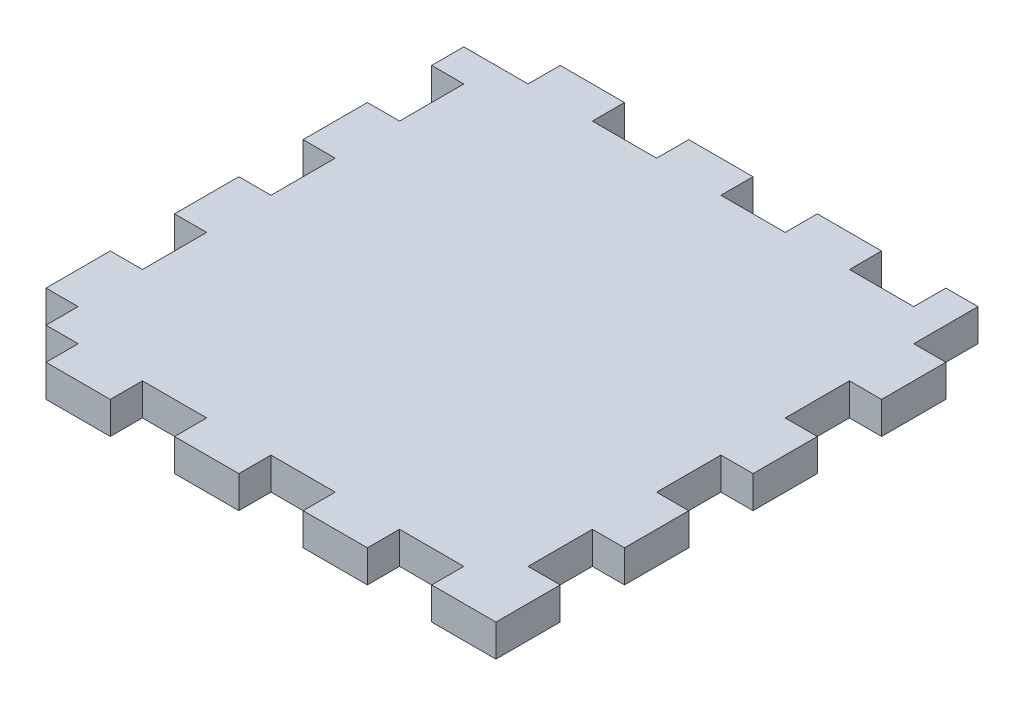
SolidWorks part; units mm, degrees
ref_plane "Front Plane" through (0, 0, 0) normal (0, 0, 1) x (1, 0, 0)
ref_plane "Top Plane" through (0, 0, 0) normal (0, 1, 0) x (1, 0, 0)
ref_plane "Right Plane" through (0, 0, 0) normal (1, 0, 0) x (0, 0, -1)
sketch "Sketch1" plane through (0, 0, 0) normal (0, 1, 0) x (1, 0, 0)
  line L1 (0, 0) -> (101.6, 0)
  line L2 (0, 0) -> (0, 101.6)
  line L3 (0, 101.6) -> (101.6, 101.6)
  line L4 (101.6, 0) -> (101.6, 101.6)
  dimension "D1" = 101.6
  dimension "D2" = 101.6
extrude "Boss-Extrude1" add sketch "Sketch1" along normal blind 6.35
ref_plane "Plane1" through (0, 0, -50.8) normal (0, 0, -1) x (-1, 0, 0)
ref_plane "Plane2" through (50.8, 0, 0) normal (-1, 0, 0) x (0, 0, 1)
sketch "Sketch2" plane through (0, 6.35, 0) normal (0, 1, 0) x (1, 0, 0)
  line L0 (6.35, 101.6) -> (6.35, 0)
  line L1 (101.6, 101.6) -> (0, 101.6) construction
  line L2 (0, 0) -> (101.6, 0) construction
  line L3 (0, 95.25) -> (101.6, 95.25)
  line L4 (0, 101.6) -> (0, 0) construction
  line L5 (101.6, 0) -> (101.6, 101.6) construction
  line L6 (12.7, 101.6) -> (12.7, 95.25)
  line L7 (0, 12.7) -> (6.35, 12.7)
  line L8 (0, 25.4) -> (6.35, 25.4)
  line L9 (0, 38.1) -> (6.35, 38.1)
  line L10 (0, 50.8) -> (6.35, 50.8)
  line L11 (0, 63.5) -> (6.35, 63.5)
  line L12 (0, 76.2) -> (6.35, 76.2)
  line L13 (0, 88.9) -> (6.35, 88.9)
  line L14 (0, 101.6) -> (6.35, 101.6)
  line L15 (25.4, 101.6) -> (25.4, 95.25)
  line L16 (38.1, 101.6) -> (38.1, 95.25)
  line L17 (50.8, 101.6) -> (50.8, 95.25)
  line L18 (63.5, 101.6) -> (63.5, 95.25)
  line L19 (76.2, 101.6) -> (76.2, 95.25)
  line L20 (88.9, 101.6) -> (88.9, 95.25)
  line L21 (101.6, 101.6) -> (101.6, 95.25)
  line L22 (95.25, 101.6) -> (95.25, 0)
  line L23 (95.25, 12.7) -> (101.6, 12.7)
  line L24 (95.25, 25.4) -> (101.6, 25.4)
  line L25 (95.25, 38.1) -> (101.6, 38.1)
  line L26 (0, 101.6) -> (0, 0)
  line L27 (0, 0) -> (101.6, 0)
  line L28 (101.6, 0) -> (101.6, 101.6)
  line L29 (101.6, 101.6) -> (0, 101.6)
  line L30 (0, 101.6) -> (0, 0)
  line L31 (0, 0) -> (101.6, 0)
  line L32 (101.6, 0) -> (101.6, 101.6)
  line L33 (101.6, 101.6) -> (0, 101.6)
  line L34 (95.25, 50.8) -> (101.6, 50.8)
  line L35 (95.25, 63.5) -> (101.6, 63.5)
  line L36 (95.25, 76.2) -> (101.6, 76.2)
  line L37 (95.25, 88.9) -> (101.6, 88.9)
  line L38 (95.25, 101.6) -> (101.6, 101.6)
  line L39 (0, 6.35) -> (101.6, 6.35)
  line L40 (12.7, 6.35) -> (12.7, 0)
  line L41 (25.4, 6.35) -> (25.4, 0)
  line L42 (38.1, 6.35) -> (38.1, 0)
  line L43 (50.8, 6.35) -> (50.8, 0)
  line L44 (63.5, 6.35) -> (63.5, 0)
  line L45 (76.2, 6.35) -> (76.2, 0)
  line L46 (88.9, 6.35) -> (88.9, 0)
  line L47 (101.6, 6.35) -> (101.6, 0)
  line M5 (0, 101.6) -> (0, 0)
  line M6 (0, 0) -> (101.6, 0)
  line M7 (101.6, 0) -> (101.6, 101.6)
  line M8 (101.6, 101.6) -> (0, 101.6)
  dimension "D1" = 6.35
  dimension "D2" = 6.35
  dimension "D3" = 12.7
  dimension "D4" = 12.7
  dimension "D7" = 6.35
  dimension "D8" = 12.7
  dimension "D10" = 6.35
  dimension "D11" = 12.7
  dimension "D6" = 0
  dimension "D5" = 8
  dimension "D9" = 8
extrude "Cut-Extrude1" cut sketch "Sketch2" against normal blind 6.35 contours L22 L37 L3 M7 | L22 L3 M8 M7 | L36 L22 L35 M7 | L34 L22 L25 M7 | L24 L22 L23 M7 | L7 L0 M5 M6 | L9 L8 L0 M5 | L11 L10 L0 M5 | L13 L12 L0 M5 region at (3.175, 6.35, -82.55) region at (3.175, 6.35, -57.15) region at (3.175, 6.35, -31.75) region at (3.175, 6.35, -9.525) region at (98.425, 6.35, -98.425) region at (98.425, 6.35, -92.075) region at (98.425, 6.35, -69.85) region at (98.425, 6.35, -44.45) region at (98.425, 6.35, -19.05)
extrude "Cut-Extrude2" cut sketch "Sketch2<3>" against normal blind 6.35 contours L6 L0 L3 M8 | L16 L15 L3 M8 | L18 L17 L3 M8 | L20 L19 L3 M8 | L46 L39 L45 M6 | L44 L39 L43 M6 | L42 L39 L41 M6 | L40 L39 L0 M6 | L39 L30 L0 M6 region at (9.525, 6.35, -98.425) region at (31.75, 6.35, -98.425) region at (57.15, 6.35, -98.425) region at (9.525, 6.35, -3.175) region at (3.175, 6.35, -3.175) region at (82.55, 6.35, -98.425) region at (31.75, 6.35, -3.175) region at (57.15, 6.35, -3.175) region at (82.55, 6.35, -3.175)
sketch "Sketch2<3>" plane through (0, 6.35, 0) normal (0, 1, 0) x (1, 0, 0) same geometry as "Sketch2"
mirror "Mirror2" about plane through (0, 0, -50.8) normal (0, 0, -1) of "Cut-Extrude2"
sketch "Sketch3" [suppressed] plane through (0, 6.35, 0) normal (0, 1, 0) x (1, 0, 0)
  line L0 (0, 50.8) -> (101.6, 50.8) construction
  line L1 (50.8, 101.6) -> (50.8, 0) construction
  line L2 (0, 6.35) -> (101.6, 6.35) construction
  line L3 (25.4, 17.78) -> (76.2, 17.78) construction
  line L4 (25.4, 22.86) -> (76.2, 22.86)
  line L5 (25.4, 12.7) -> (76.2, 12.7)
  arc A0 (25.4, 22.86) -> (25.4, 12.7) centre (25.4, 17.78) ccw
  arc A1 (76.2, 12.7) -> (76.2, 22.86) centre (76.2, 17.78) ccw
  point P14 (50.8, 17.78)
  dimension "D2" = 5.08
  dimension "D1" = 6.35
  dimension "D3" = 50.8
extrude "Cut-Extrude3" [suppressed] cut sketch "Sketch3" against normal blind 6.35
equation "\"acrillic thick\"= 0.25"
equation "\"D1@Boss-Extrude1\"=\"acrillic thick\""
equation "\"D1@Sketch2\"=\"acrillic thick\""
equation "\"D2@Sketch2\"=\"acrillic thick\""
equation "\"D7@Sketch2\"=\"acrillic thick\""
equation "\"D10@Sketch2\"=\"acrillic thick\""
equation "\"D1@Cut-Extrude3\"=\"acrillic thick\""
